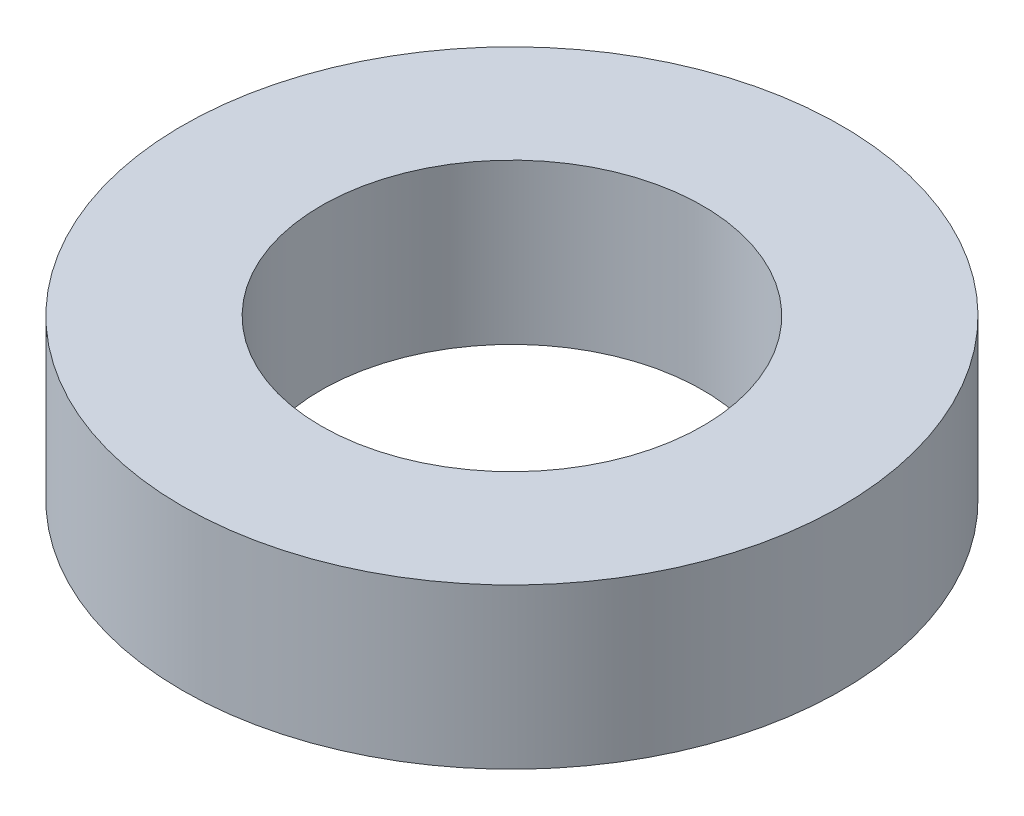
SolidWorks part; units mm, degrees
ref_plane "Front Plane" through (0, 0, 0) normal (0, 0, 1) x (1, 0, 0)
ref_plane "Top Plane" through (0, 0, 0) normal (0, 1, 0) x (1, 0, 0)
ref_plane "Right Plane" through (0, 0, 0) normal (1, 0, 0) x (0, 0, -1)
sketch "Sketch1" plane through (0, 0, 0) normal (0, 1, 0) x (1, 0, 0)
  circle A0 centre (0, 0) radius 47.5
  dimension "FLANGE_OD" = 95
extrude "Boss-Extrude1" add sketch "Sketch1" along normal blind 23
sketch "Sketch2" plane through (0, 0, 0) normal (0, 1, 0) x (1, 0, 0)
  circle A0 centre (0, 0) radius 27.5
  dimension "BORE_D" = 55
extrude "Cut-Extrude1" cut sketch "Sketch2" along normal through all
sketch "Sketch3" plane through (0, 23, 0) normal (0, 1, 0) x (1, 0, 0)
  circle A0 centre (0, 0) radius 16.0163 construction
  circle A1 centre (-16.0163, 0) radius 3.2414
  dimension "BOLT_D" = 6.4827
  dimension "BOLT_PCD" = 32.0327
extrude "Cut-Extrude2" cut sketch "Sketch3" against normal blind 14.6005 rebuild error yes
pattern_circular "CirPattern1" count 4 over 360 rebuild error yes
